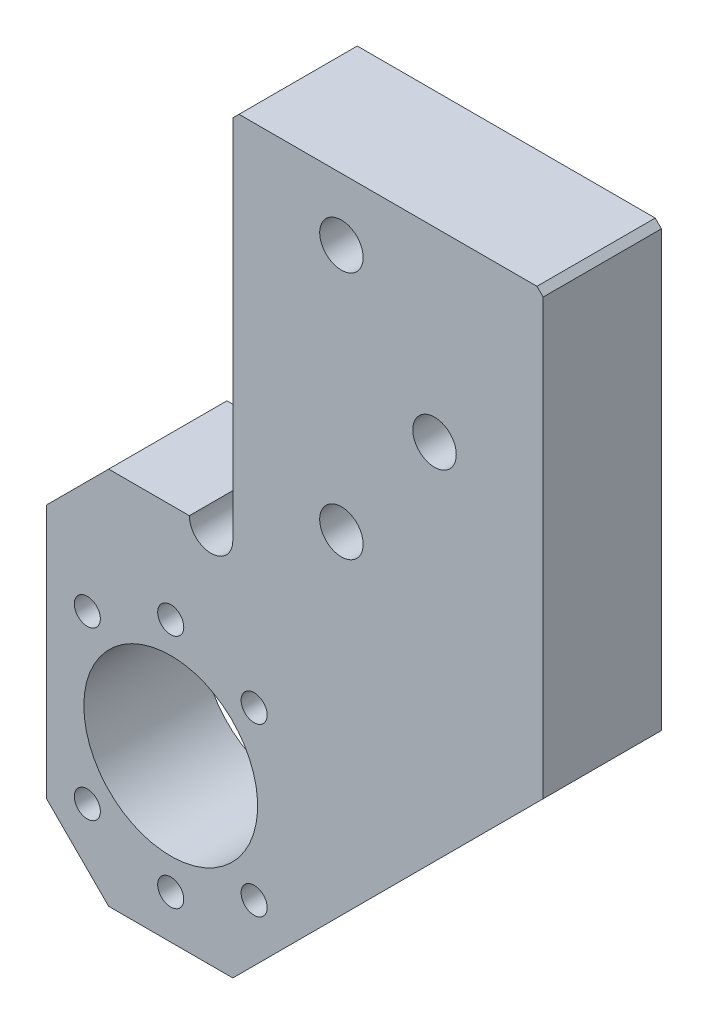
SolidWorks part; units mm, degrees
material "6061-T6 (SS)"
ref_plane "Front Plane" through (0, 0, 0) normal (0, 0, 1) x (1, 0, 0)
ref_plane "Top Plane" through (0, 0, 0) normal (0, 1, 0) x (1, 0, 0)
ref_plane "Right Plane" through (0, 0, 0) normal (1, 0, 0) x (0, 0, -1)
sketch "Sketch1" plane through (0, 0, 0) normal (0, 0, 1) x (1, 0, 0)
  line L0 (3, 35) -> (-10, 35)
  line L1 (-10, 35) -> (-20, 25)
  line L2 (-20, 25) -> (-20, -16)
  line L3 (-20, -16) -> (-10, -26)
  line L4 (-10, -26) -> (10, -26)
  line L5 (10, -26) -> (60, 24)
  line L6 (60, 24) -> (60, 95)
  line L7 (60, 95) -> (10, 95)
  line L8 (10, 95) -> (10, 35)
  line L9 (0, -10.4775) -> (0, 10.4775) construction
  line L10 (-10, -26) -> (-10, 35) construction
  line L12 (27.5, 85) -> (42.5, 85) construction
  line L13 (27.5, 85) -> (27.5, 45) construction
  line L14 (27.5, 45) -> (42.5, 45) construction
  line L15 (42.5, 85) -> (42.5, 45) construction
  line L16 (0, -19) -> (13.435, -13.435) construction
  line L17 (13.435, -13.435) -> (19, 0) construction
  line L18 (19, 0) -> (13.435, 13.435) construction
  line L19 (13.435, 13.435) -> (0, 19) construction
  line L20 (0, 19) -> (-13.435, 13.435) construction
  line L21 (-13.435, 13.435) -> (-19, 0) construction
  line L22 (-19, 0) -> (-13.435, -13.435) construction
  line L23 (-13.435, -13.435) -> (0, -19) construction
  circle A0 centre (0, 0) radius 14
  arc A1 (10, 35) -> (3, 35) centre (6.5, 35) cw
  circle A2 centre (0, 0) radius 17.5537 construction
  point P14 (0, -26)
  point P21 (42.5, 65)
  point P22 (27.5, 85)
  point P23 (0, 0)
  point P24 (27.5, 45)
  dimension "D1" = 28
  dimension "D6" = 3.5
  dimension "D2" = 20
  dimension "D3" = 26
  dimension "D4" = 35
  dimension "D5" = 20
  dimension "D7" = 10
  dimension "D8" = 17.5
  dimension "D9" = 10
  dimension "D10" = 17.5
  dimension "D11" = 15
  dimension "D12" = 10
  dimension "D13" = 40
  dimension "D14" = 38
extrude "Boss-Extrude1" add sketch "Sketch1" along normal mid plane 19.05
hole_wizard "M8x1.0 Tapped Hole1" positions "Sketch2" profile "Sketch3" tap size "M8x1.0" standard "ANSI Metric" end condition up to next
sketch "Sketch2" plane through (0, 0, 9.525) normal (0, 0, 1) x (1, 0, 0)
  line L0 (42.5, 85) -> (42.5, 45) construction
  point P0 (27.5, 45)
  point P3 (42.5, 65)
  point P7 (27.5, 85)
sketch "Sketch3" plane through (27.5, 45, 9.525) normal (1, 0, 0) x (0, -1, 0)
  line L0 (0, 0) -> (0, 19.05)
  line L1 (0, 19.05) -> (3.5, 19.05)
  line L2 (3.5, 19.05) -> (3.5, 0)
  line L5 (3.5, 0) -> (0, 0)
  line L11 (0, -6.35) -> (0, 107.95) construction
  dimension "Thru Tap Drill Dia." = 7
  dimension "Thru Tap Drill Depth" = 19.05
cosmetic thread "Hole Thread1" parameters "D2"=8
cosmetic thread "Hole Thread2" parameters "D2"=8
cosmetic thread "Hole Thread3" parameters "D2"=8
hole_wizard "M5x0.8 Tapped Hole1" positions "Sketch4" profile "Sketch5" tap size "M5x0.8" standard "ANSI Metric" end condition up to next
sketch "Sketch4" plane through (0, 0, 9.525) normal (0, 0, 1) x (1, 0, 0)
  point P0 (0, 19)
  point P3 (-13.435, 13.435)
  point P6 (13.435, 13.435)
  point P9 (13.435, -13.435)
  point P12 (0, -19)
  point P15 (-13.435, -13.435)
sketch "Sketch5" plane through (0, 19, 9.525) normal (1, 0, 0) x (0, -1, 0)
  line L0 (0, 0) -> (0, 19.05)
  line L1 (0, 19.05) -> (2.1, 19.05)
  line L2 (2.1, 19.05) -> (2.1, 0)
  line L5 (2.1, 0) -> (0, 0)
  line L11 (0, -6.35) -> (0, 107.95) construction
  dimension "Thru Tap Drill Dia." = 4.2
  dimension "Thru Tap Drill Depth" = 19.05
cosmetic thread "Hole Thread4" parameters "D2"=5
cosmetic thread "Hole Thread5" parameters "D2"=5
cosmetic thread "Hole Thread6" parameters "D2"=5
cosmetic thread "Hole Thread7" parameters "D2"=5
cosmetic thread "Hole Thread8" parameters "D2"=5
cosmetic thread "Hole Thread9" parameters "D2"=5
chamfer "Chamfer1" distance 1 2 edges at (10, 95, 0) (60, 95, 0)
